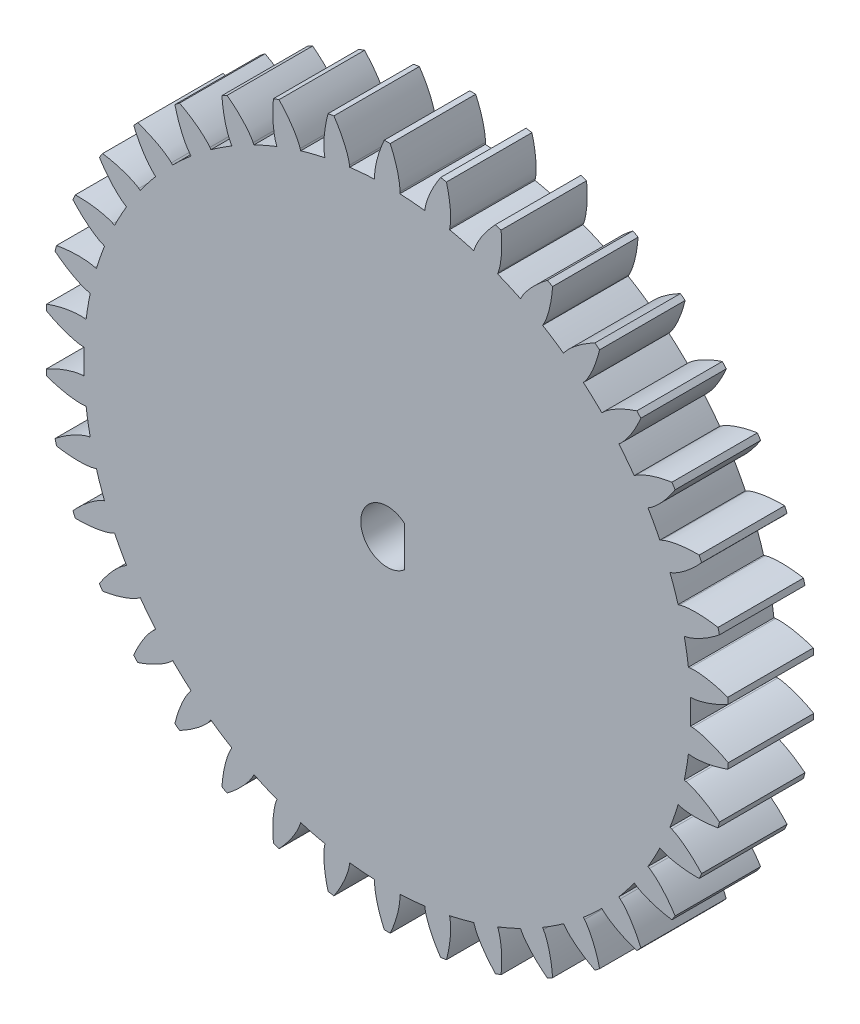
SolidWorks part; units mm, degrees
ref_plane "前视基准面" through (0, 0, 0) normal (0, 0, 1) x (1, 0, 0)
ref_plane "上视基准面" through (0, 0, 0) normal (0, 1, 0) x (1, 0, 0)
ref_plane "右视基准面" through (0, 0, 0) normal (1, 0, 0) x (0, 0, -1)
other "Configuration Table"
sketch "草图1" plane through (0, 0, 0) normal (0, 0, 1) x (1, 0, 0)
  line L0 (0, 0) -> (4, 0) construction
  line L1 (0, 0) -> (3.9231, 0.7804) construction
  line L2 (0, 0) -> (3.6941, 0.6945)
  line L3 (3.9231, 0.7804) -> (3.9231, -0.7804) construction
  line L4 (0, 0) -> (3.6941, -0.6945)
  circle A0 centre (0, 0) radius 5
  circle A1 centre (0, 0) radius 4 construction
  circle A2 centre (0, 0) radius 2.75
  circle A3 centre (0, 0) radius 3.7588 construction
  circle A4 centre (0, 0) radius 1.5
  spline S0 degree 4 poles (3.6941, 0.6945) (3.7222, 0.6998) (3.7997, 0.7204) (3.9403, 0.7826) (4.1522, 0.9137) (4.3976, 1.1246) (4.671, 1.4371) (4.933, 1.8476) (5.1531, 2.335) (5.3561, 3.0262) (5.443, 3.7431) (5.4253, 4.4924) (5.2827, 5.3729) (5.0281, 6.2292) (4.5902, 7.1708) (3.9479, 8.1289) (3.1749, 8.9843) (2.2938, 9.7273) (1.3255, 10.3516) (0.2887, 10.8537) (-0.7988, 11.2323) (-1.7817, 11.4556) (-2.5647, 11.5617) (-3.139, 11.6038) (-3.4958, 11.6181) (-3.788, 11.6215) (-4.0656, 11.6193) (-4.3699, 11.6068) (-4.6041, 11.5939) (-4.8725, 11.5704) (-5.1429, 11.5429) (-5.4129, 11.5084) (-5.885, 11.4372) (-6.2665, 11.3559) (-6.6616, 11.2688) (-6.8509, 11.2136) (-6.9779, 11.1808) knots 0 0 0 0 0 0.005604 0.015718 0.02996 0.048734 0.068727 0.096889 0.125051 0.153212 0.209535 0.237696 0.271429 0.327752 0.384075 0.440398 0.496721 0.553044 0.609367 0.66569 0.722013 0.778336 0.806497 0.820578 0.834659 0.84874 0.86282 0.876901 0.890982 0.900036 0.909091 0.931818 0.954545 0.977273 1 1 1 1 1 construction
  spline S1 degree 4 poles (3.6941, 0.6945) (3.7222, 0.6998) (3.7997, 0.7204) (3.9403, 0.7826) (4.1522, 0.9137) (4.3976, 1.1246) (4.671, 1.4371) (4.933, 1.8476) (5.1531, 2.335) (5.3561, 3.0262) (5.443, 3.7431) (5.4253, 4.4924) (5.2827, 5.3729) (5.0281, 6.2292) (4.5902, 7.1708) (3.9479, 8.1289) (3.1749, 8.9843) (2.2938, 9.7273) (1.3255, 10.3516) (0.2887, 10.8537) (-0.7988, 11.2323) (-1.7817, 11.4556) (-2.5647, 11.5617) (-3.139, 11.6038) (-3.4958, 11.6181) (-3.788, 11.6215) (-4.0656, 11.6193) (-4.3699, 11.6068) (-4.6041, 11.5939) (-4.8725, 11.5704) (-5.031, 11.5543) (-5.1147, 11.5449) (-5.1564, 11.5399) knots 0 0 0 0 0 0.005604 0.015718 0.02996 0.048734 0.068727 0.096889 0.125051 0.153212 0.209535 0.237696 0.271429 0.327752 0.384075 0.440398 0.496721 0.553044 0.609367 0.66569 0.722013 0.778336 0.806497 0.820578 0.834659 0.84874 0.86282 0.876901 0.890982 0.900036 0.909091 0.909091 0.909091 0.909091 0.909091
  spline S2 degree 4 poles (3.6941, -0.6945) (3.7222, -0.6998) (3.7997, -0.7204) (3.9403, -0.7826) (4.1522, -0.9137) (4.3976, -1.1246) (4.671, -1.4371) (4.933, -1.8476) (5.1531, -2.335) (5.3561, -3.0262) (5.443, -3.7431) (5.4253, -4.4924) (5.2827, -5.3729) (5.0281, -6.2292) (4.5902, -7.1708) (3.9479, -8.1289) (3.1749, -8.9843) (2.2938, -9.7273) (1.3255, -10.3516) (0.2887, -10.8537) (-0.7988, -11.2323) (-1.7817, -11.4556) (-2.5647, -11.5617) (-3.139, -11.6038) (-3.4958, -11.6181) (-3.788, -11.6215) (-4.0656, -11.6193) (-4.3699, -11.6068) (-4.6041, -11.5939) (-4.8725, -11.5704) (-5.1429, -11.5429) (-5.4129, -11.5084) (-5.885, -11.4372) (-6.2665, -11.3559) (-6.6616, -11.2688) (-6.8509, -11.2136) (-6.9779, -11.1808) knots 0 0 0 0 0 0.005604 0.015718 0.02996 0.048734 0.068727 0.096889 0.125051 0.153212 0.209535 0.237696 0.271429 0.327752 0.384075 0.440398 0.496721 0.553044 0.609367 0.66569 0.722013 0.778336 0.806497 0.820578 0.834659 0.84874 0.86282 0.876901 0.890982 0.900036 0.909091 0.931818 0.954545 0.977273 1 1 1 1 1 construction
  spline S3 degree 4 poles (3.6941, -0.6945) (3.7222, -0.6998) (3.7997, -0.7204) (3.9403, -0.7826) (4.1522, -0.9137) (4.3976, -1.1246) (4.671, -1.4371) (4.933, -1.8476) (5.1531, -2.335) (5.3561, -3.0262) (5.443, -3.7431) (5.4253, -4.4924) (5.2827, -5.3729) (5.0281, -6.2292) (4.5902, -7.1708) (3.9479, -8.1289) (3.1749, -8.9843) (2.2938, -9.7273) (1.3255, -10.3516) (0.2887, -10.8537) (-0.7988, -11.2323) (-1.7817, -11.4556) (-2.5647, -11.5617) (-3.139, -11.6038) (-3.4958, -11.6181) (-3.788, -11.6215) (-4.0656, -11.6193) (-4.3699, -11.6068) (-4.6041, -11.5939) (-4.8725, -11.5704) (-5.031, -11.5543) (-5.1147, -11.5449) (-5.1564, -11.5399) knots 0 0 0 0 0 0.005604 0.015718 0.02996 0.048734 0.068727 0.096889 0.125051 0.153212 0.209535 0.237696 0.271429 0.327752 0.384075 0.440398 0.496721 0.553044 0.609367 0.66569 0.722013 0.778336 0.806497 0.820578 0.834659 0.84874 0.86282 0.876901 0.890982 0.900036 0.909091 0.909091 0.909091 0.909091 0.909091
  point P15 (3.9231, 0)
  dimension "齿顶圆直径" = 10
  dimension "分度圆直径" = 8
  dimension "齿根圆直径" = 5.5
  dimension "基圆直径" = 7.5175
  dimension "内孔直径" = 3
  dimension "渐近线镜像线夹角" = 11.25
extrude "凸台-拉伸1" add sketch "草图1" along normal blind 5 contours A0 | A4
extrude "切除-拉伸1" cut sketch "草图1<3>" along normal through all contours A2 S3 A0 S1 region at (4.0533, 0, 0)
sketch "草图1<3>" plane through (0, 0, 0) normal (0, 0, 1) x (1, 0, 0) same geometry as "草图1"
fillet "圆角1" radius 0.5 4 edges at (2.7027, 0.5081, 2.5) (2.7027, -0.5081, 2.5) (4.7472, 1.5696, 2.5) (4.7472, -1.5696, 2.5)
pattern_circular "阵列(圆周)1" count 8 every 45 about axis through (0, 0, 5) along (0, 0, 1) of "切除-拉伸1", "圆角1"
sketch "草图2" plane through (0, 0, 5) normal (0, 0, 1) x (1, 0, 0)
  line L0 (0, 0) -> (19, 0) construction
  line L1 (0, 0) -> (17.8389, 0.7378)
  line L2 (0, 0) -> (17.8389, -0.7378)
  line L3 (17.8389, 0.7378) -> (17.8389, -0.7378) construction
  circle A0 centre (0, 0) radius 19 construction
  circle A1 centre (0, 0) radius 17.8542 construction
  circle A2 centre (0, 0) radius 17.75
  circle A3 centre (0, 0) radius 20
  circle A4 centre (0, 0) radius 1.5
  spline S0 degree 4 poles (17.8389, -0.7378) (17.8728, -0.7392) (17.9406, -0.7441) (18.0752, -0.7621) (18.3288, -0.8123) (18.6635, -0.9051) (19.1205, -1.0702) (19.658, -1.3153) (20.4669, -1.7609) (21.5195, -2.5027) (22.8507, -3.7145) (24.3091, -5.5094) (25.6114, -7.6908) (26.6766, -10.2121) (27.4216, -12.8444) (27.8645, -15.543) (28.0306, -18.4074) (27.8656, -21.9567) (27.1273, -26.1356) (25.5694, -30.8158) (23.0564, -35.6845) (20.2692, -39.5823) (17.5235, -42.6283) (15.0272, -44.9572) (12.9164, -46.6904) (10.7035, -48.2904) (8.3975, -49.7545) (5.4145, -51.4121) (1.6874, -53.1227) (-2.8247, -54.7082) (-7.1558, -55.7237) (-10.5228, -56.2445) (-12.9095, -56.489) (-14.244, -56.5948) (-15.5428, -56.66) (-16.5612, -56.6949) (-17.638, -56.7056) (-18.2041, -56.705) (-18.894, -56.6964) (-19.4423, -56.6837) (-20.126, -56.6612) (-20.9547, -56.6234) (-21.9141, -56.5638) (-23.0135, -56.4746) (-24.1084, -56.3645) (-25.2027, -56.2336) (-26.0203, -56.1199) (-26.5651, -56.0373) (-26.8369, -55.9943) knots 0 0 0 0 0 0.001401 0.002802 0.005604 0.010661 0.015718 0.022839 0.02996 0.048734 0.068727 0.096889 0.125051 0.153212 0.181374 0.209535 0.237696 0.271429 0.327752 0.384075 0.440398 0.496721 0.524883 0.553044 0.581206 0.609367 0.637529 0.66569 0.722013 0.778336 0.834659 0.84874 0.86282 0.876901 0.890982 0.900036 0.909091 0.914773 0.920455 0.926136 0.931818 0.943182 0.954545 0.965909 0.977273 0.988636 1 1 1 1 1 construction
  spline S1 degree 4 poles (17.8389, -0.7378) (17.8728, -0.7392) (17.9406, -0.7441) (18.0752, -0.7621) (18.3288, -0.8123) (18.6635, -0.9051) (19.1205, -1.0702) (19.658, -1.3153) (20.4669, -1.7609) (21.5195, -2.5027) (22.8507, -3.7145) (24.3091, -5.5094) (25.6114, -7.6908) (26.6766, -10.2121) (27.4216, -12.8444) (27.8645, -15.543) (28.0306, -18.4074) (27.8656, -21.9567) (27.1273, -26.1356) (25.5694, -30.8158) (23.0564, -35.6845) (20.2692, -39.5823) (17.5235, -42.6283) (15.0272, -44.9572) (12.9164, -46.6904) (10.7035, -48.2904) (8.3975, -49.7545) (5.4145, -51.4121) (1.6874, -53.1227) (-2.8247, -54.7082) (-7.1558, -55.7237) (-10.5228, -56.2445) (-12.9095, -56.489) (-14.244, -56.5948) (-15.5428, -56.66) (-16.5612, -56.6949) (-17.4764, -56.704) (-17.8641, -56.7049) (-18.0636, -56.7042) knots 0 0 0 0 0 0.001401 0.002802 0.005604 0.010661 0.015718 0.022839 0.02996 0.048734 0.068727 0.096889 0.125051 0.153212 0.181374 0.209535 0.237696 0.271429 0.327752 0.384075 0.440398 0.496721 0.524883 0.553044 0.581206 0.609367 0.637529 0.66569 0.722013 0.778336 0.834659 0.84874 0.86282 0.876901 0.890982 0.900036 0.909091 0.909091 0.909091 0.909091 0.909091
  spline S2 degree 4 poles (17.8389, 0.7378) (17.8728, 0.7392) (17.9406, 0.7441) (18.0752, 0.7621) (18.3288, 0.8123) (18.6635, 0.9051) (19.1205, 1.0702) (19.658, 1.3153) (20.4669, 1.7609) (21.5195, 2.5027) (22.8507, 3.7145) (24.3091, 5.5094) (25.6114, 7.6908) (26.6766, 10.2121) (27.4216, 12.8444) (27.8645, 15.543) (28.0306, 18.4074) (27.8656, 21.9567) (27.1273, 26.1356) (25.5694, 30.8158) (23.0564, 35.6845) (20.2692, 39.5823) (17.5235, 42.6283) (15.0272, 44.9572) (12.9164, 46.6904) (10.7035, 48.2904) (8.3975, 49.7545) (5.4145, 51.4121) (1.6874, 53.1227) (-2.8247, 54.7082) (-7.1558, 55.7237) (-10.5228, 56.2445) (-12.9095, 56.489) (-14.244, 56.5948) (-15.5428, 56.66) (-16.5612, 56.6949) (-17.638, 56.7056) (-18.2041, 56.705) (-18.894, 56.6964) (-19.4423, 56.6837) (-20.126, 56.6612) (-20.9547, 56.6234) (-21.9141, 56.5638) (-23.0135, 56.4746) (-24.1084, 56.3645) (-25.2027, 56.2336) (-26.0203, 56.1199) (-26.5651, 56.0373) (-26.8369, 55.9943) knots 0 0 0 0 0 0.001401 0.002802 0.005604 0.010661 0.015718 0.022839 0.02996 0.048734 0.068727 0.096889 0.125051 0.153212 0.181374 0.209535 0.237696 0.271429 0.327752 0.384075 0.440398 0.496721 0.524883 0.553044 0.581206 0.609367 0.637529 0.66569 0.722013 0.778336 0.834659 0.84874 0.86282 0.876901 0.890982 0.900036 0.909091 0.914773 0.920455 0.926136 0.931818 0.943182 0.954545 0.965909 0.977273 0.988636 1 1 1 1 1 construction
  spline S3 degree 4 poles (17.8389, 0.7378) (17.8728, 0.7392) (17.9406, 0.7441) (18.0752, 0.7621) (18.3288, 0.8123) (18.6635, 0.9051) (19.1205, 1.0702) (19.658, 1.3153) (20.4669, 1.7609) (21.5195, 2.5027) (22.8507, 3.7145) (24.3091, 5.5094) (25.6114, 7.6908) (26.6766, 10.2121) (27.4216, 12.8444) (27.8645, 15.543) (28.0306, 18.4074) (27.8656, 21.9567) (27.1273, 26.1356) (25.5694, 30.8158) (23.0564, 35.6845) (20.2692, 39.5823) (17.5235, 42.6283) (15.0272, 44.9572) (12.9164, 46.6904) (10.7035, 48.2904) (8.3975, 49.7545) (5.4145, 51.4121) (1.6874, 53.1227) (-2.8247, 54.7082) (-7.1558, 55.7237) (-10.5228, 56.2445) (-12.9095, 56.489) (-14.244, 56.5948) (-15.5428, 56.66) (-16.5612, 56.6949) (-17.4764, 56.704) (-17.8641, 56.7049) (-18.0636, 56.7042) knots 0 0 0 0 0 0.001401 0.002802 0.005604 0.010661 0.015718 0.022839 0.02996 0.048734 0.068727 0.096889 0.125051 0.153212 0.181374 0.209535 0.237696 0.271429 0.327752 0.384075 0.440398 0.496721 0.524883 0.553044 0.581206 0.609367 0.637529 0.66569 0.722013 0.778336 0.834659 0.84874 0.86282 0.876901 0.890982 0.900036 0.909091 0.909091 0.909091 0.909091 0.909091
  point P16 (17.8389, 0)
  dimension "内孔直径" = 3
  dimension "分度圆直径" = 38
  dimension "齿顶圆直径" = 40
  dimension "基圆直径" = 35.7083
  dimension "齿根圆直径" = 35.5
  dimension "渐开线镜像线夹角" = 2.368
extrude "凸台-拉伸2" add sketch "草图2" along normal blind 5 contours A3 | A4
extrude "切除-拉伸3" cut sketch "草图2<3>" along normal through all contours S3 L1 A2 L2 S1 A3 region at (19.0065, 0, 5)
sketch "草图2<3>" plane through (0, 0, 5) normal (0, 0, 1) x (1, 0, 0) same geometry as "草图2"
pattern_circular "阵列(圆周)2" count 38 over 360 about axis through (0, 0, 10) along (0, 0, 1) of "切除-拉伸3"
sketch "草图3" plane through (0, 0, 0) normal (0, 0, -1) x (-1, 0, 0)
  line L0 (-1, -1.1843) -> (-1, 1.1843)
  circle A0 centre (0, 0) radius 1.55
  dimension "D1" = 3.1
  dimension "D2" = 1
extrude "凸台-拉伸3" add sketch "草图3" against normal through all contours A0
extrude "切除-拉伸4" cut sketch "草图3<3>" against normal through all contours L0 region at (-0.1667, 0, 0)
sketch "草图3<3>" plane through (0, 0, 0) normal (0, 0, -1) x (-1, 0, 0) same geometry as "草图3"
sketch "草图4" plane through (0, 0, 5) normal (0, 0, -1) x (-1, 0, 0)
  circle A0 centre (0, 0) radius 10
  dimension "D1" = 20
extrude "切除-拉伸5" cut sketch "草图4" along normal through all
equation "\"m\"= 1'模数"
equation "\"z\"= 8'齿数"
equation "\"a\"= 20度'压力角"
equation "\"d\"= \"m\" * \"z\"'分度圆直径"
equation "\"da\"= ( \"z\" + 2 ) * \"m\"'齿顶圆直径"
equation "\"df\"= ( \"z\" - 2.5 ) * \"m\"'齿根圆直径"
equation "\"s\"= 0.5 * PI * \"m\"'分度圆齿厚"
equation "\"r\"= 0.38 * \"m\"'齿根圆角"
equation "\"B\"= 0.3 * \"d\"'齿厚"
equation "\"db\"= \"m\" * \"z\" * cos ( \"a\" )'基圆直径"
equation "\"rb\"= \"db\" / 2'基圆半径"
equation "\"齿顶圆直径@草图1\"= \"da\""
equation "\"分度圆直径@草图1\"= \"d\""
equation "\"齿根圆直径@草图1\"= \"df\""
equation "\"基圆直径@草图1\"= \"db\""
equation "\"渐近线镜像线夹角@草图1\"= 360 / 4 / \"z\""
equation "\"h\"= 5'齿轮厚度"
equation "\"ir\"= 3'内孔直径"
equation "\"内孔直径@草图1\"= \"ir\""
equation "\"齿轮厚@凸台-拉伸1\"= \"h\""
equation "\"齿轮夹角@阵列(圆周)1\"= 360 / \"z\""
equation "\"齿数@阵列(圆周)1\"= \"z\""
equation "\"m1\"= 1'模数"
equation "\"z1\"= 38'齿数"
equation "\"a1\"= 20度'压力角"
equation "\"d1\"= \"m1\" * \"z1\"'分度圆直径"
equation "\"da1\"= ( \"z1\" + 2 ) * \"m1\"'齿顶圆直径"
equation "\"df1\"= ( \"z1\" - 2.5 ) * \"m1\"'齿根圆直径"
equation "\"s1\"= 0.5 * PI * \"m1\"'分度圆齿厚"
equation "\"r1\"= 0.38 * \"m1\"'齿根圆角"
equation "\"B1\"= 0.3 * \"d1\"'齿厚"
equation "\"db1\"= \"m1\" * \"z1\" * cos ( \"a1\" )'基圆直径"
equation "\"rb1\"= \"db1\" / 2'基圆半径"
equation "\"分度圆直径@草图2\"= \"d1\""
equation "\"齿顶圆直径@草图2\"= \"da1\""
equation "\"基圆直径@草图2\"= \"db1\""
equation "\"齿根圆直径@草图2\"= \"df1\""
equation "\"渐开线镜像线夹角@草图2\"= 360 / 4 / \"z1\""
equation "\"内孔直径@草图2\"= \"ir\""
equation "\"二层齿轮厚@凸台-拉伸2\" = \"h1\""
equation "\"h1\"= 5'齿轮厚度"
equation "\"二层齿数@阵列(圆周)2\"= \"z1\""
